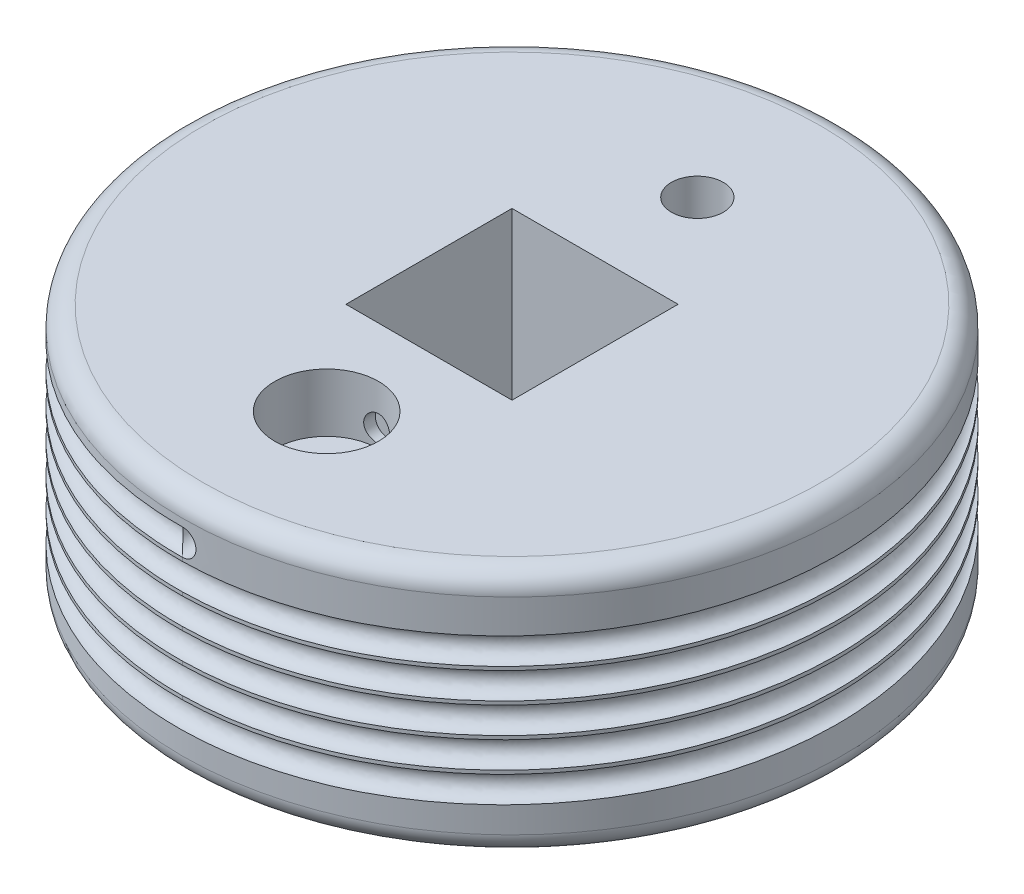
SolidWorks part; units mm, degrees
ref_plane "Front Plane" through (0, 0, 0) normal (0, 0, 1) x (1, 0, 0)
ref_plane "Top Plane" through (0, 0, 0) normal (0, 1, 0) x (1, 0, 0)
ref_plane "Right Plane" through (0, 0, 0) normal (1, 0, 0) x (0, 0, -1)
sketch "Sketch1" plane through (0, 0, 0) normal (0, 1, 0) x (1, 0, 0)
  line L1 (-3.2004, 3.2004) -> (3.2004, 3.2004)
  line L2 (-3.2004, 3.2004) -> (-3.2004, -3.2004)
  line L3 (-3.2004, -3.2004) -> (3.2004, -3.2004)
  line L4 (3.2004, 3.2004) -> (3.2004, -3.2004)
  line L5 (-3.2004, 3.2004) -> (3.2004, -3.2004) construction
  line L6 (-3.2004, -3.2004) -> (3.2004, 3.2004) construction
  circle A0 centre (0, 0) radius 12.7
  dimension "D1" = 25.4
  dimension "D2" = 6.4008
extrude "Boss-Extrude1" add sketch "Sketch1" along normal blind 9.525
ref_plane "Plane1" through (0, 1.5875, 0) normal (0, -1, 0) x (-1, 0, 0)
sketch "Sketch2" plane through (0, 1.5875, 0) normal (0, -1, 0) x (-1, 0, 0)
  circle A0 centre (0, 0) radius 12.7 construction
  circle A1 centre (0, 0) radius 12.7
curve "Helix/Spiral1" pitch 1.1545 height 6.35 radius 12.7 centre (0, 1.5875, 0) axis (0, 1, 0) start towards (0, 0, -1)
sweep "Cut-Sweep1" cut path "Helix/Spiral1" align with end faces yes circular profile diameter 1.016 parameters "D3"=1.016
ref_plane "Plane2" through (0, 0, 12.7) normal (0, 0, 1) x (1, 0, 0)
sketch "Sketch22" plane through (0, 0, 12.7) normal (0, 0, 1) x (1, 0, 0)
  line L0 (-0.0073, 8.4454) -> (0.0073, 7.4296) construction
  circle A0 centre (0, 7.9375) radius 0.508
extrude "Cut-Extrude1" cut sketch "Sketch22" against normal blind 7.9375
sketch "Sketch23" plane through (0, 9.525, 0) normal (0, 1, 0) x (1, 0, 0)
  circle A0 centre (0, -7.1437) radius 1
  dimension "D2" = 2
  dimension "D1" = 7.1437
extrude "Cut-Extrude2" cut sketch "Sketch23" against normal blind 9.525
sketch "Sketch24" plane through (0, 9.525, 0) normal (0, 1, 0) x (1, 0, 0)
  circle A0 centre (0, -7.1437) radius 2
  dimension "D1" = 4
extrude "Cut-Extrude3" cut sketch "Sketch24" against normal blind 2.25
ref_plane "Plane3" through (0, 0, -12.7) normal (0, 0, -1) x (-1, 0, 0)
sketch "Sketch25" plane through (0, 0, -12.7) normal (0, 0, -1) x (-1, 0, 0)
  line L0 (0.0073, 1.0796) -> (-0.0073, 2.0954) construction
  circle A0 centre (0, 1.5875) radius 0.508
extrude "Cut-Extrude4" cut sketch "Sketch25" against normal blind 7.9375
sketch "Sketch29" plane through (0, 0, 0) normal (0, -1, 0) x (1, 0, 0)
  circle A0 centre (0, -7.1437) radius 1
  circle A1 centre (0, 7.1437) radius 1 construction
  dimension "D1" = 7.1437
extrude "Cut-Extrude5" cut sketch "Sketch29" against normal blind 9.525
sketch "Sketch30" plane through (0, 0, 0) normal (0, -1, 0) x (1, 0, 0)
  circle A0 centre (0, -7.1437) radius 2
  dimension "D1" = 4
extrude "Cut-Extrude6" cut sketch "Sketch30" against normal blind 2.25
fillet "Fillet1" radius 0.7937 2 edges at (0, 0, 12.7) (0, 9.525, 12.7)
